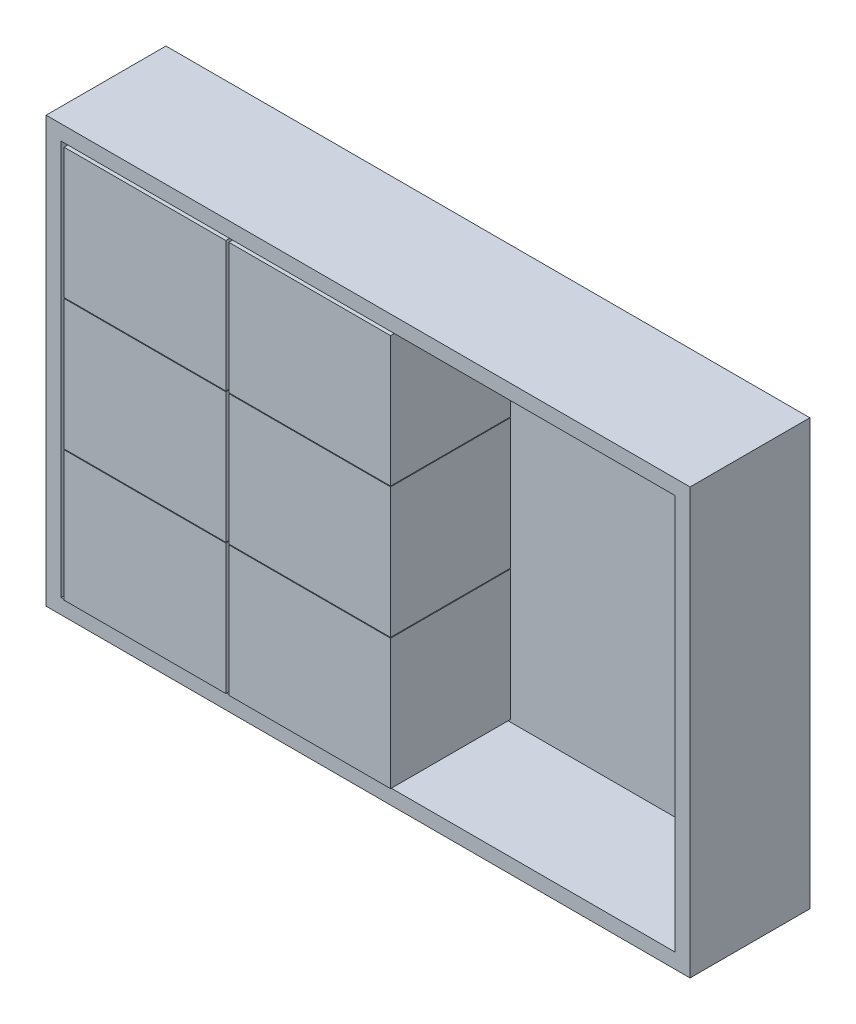
SolidWorks part; units mm, degrees
ref_plane "Plan de face" through (0, 0, 0) normal (0, 0, 1) x (1, 0, 0)
ref_plane "Plan de dessus" through (0, 0, 0) normal (0, 1, 0) x (1, 0, 0)
ref_plane "Plan de droite" through (0, 0, 0) normal (1, 0, 0) x (0, 0, -1)
sketch "Esquisse1" plane through (0, 0, 0) normal (0, 0, 1) x (1, 0, 0)
  line L1 (0, 0) -> (205, 0)
  line L2 (0, 0) -> (0, 132)
  line L3 (0, 132) -> (205, 132)
  line L4 (205, 0) -> (205, 132)
  dimension "D1" = 205
  dimension "D2" = 132
extrude "Boss.-Extru.1" add sketch "Esquisse1" along normal blind 1
extrude "Extru.-Mince1" add sketch "Esquisse1<2>" along normal blind 40 thin thin type one direction wall 5
sketch "Esquisse1<2>" plane through (0, 0, 0) normal (0, 0, 1) x (1, 0, 0) same geometry as "Esquisse1"
sketch "Esquisse2" plane through (0, 0, 1) normal (0, 0, 1) x (1, 0, 0)
  line L0 (205, 132) -> (0, 132) construction
  line L1 (2, 131.75) -> (56, 131.75)
  line L2 (2, 131.75) -> (2, 88.25)
  line L3 (2, 88.25) -> (56, 88.25)
  line L4 (56, 131.75) -> (56, 88.25)
  line L5 (0, 132) -> (0, 0) construction
  dimension "D1" = 54
  dimension "D2" = 43.5
  dimension "D3" = 0.25
  dimension "D4" = 2
extrude "Boss.-Extru.2" add sketch "Esquisse2" along normal blind 40
pattern_linear "Répétition linéaire1" count 3 spacing 43.75 along (0, -1, 0) count 2 spacing 55 along (1, 0, 0) of "Boss.-Extru.2"
